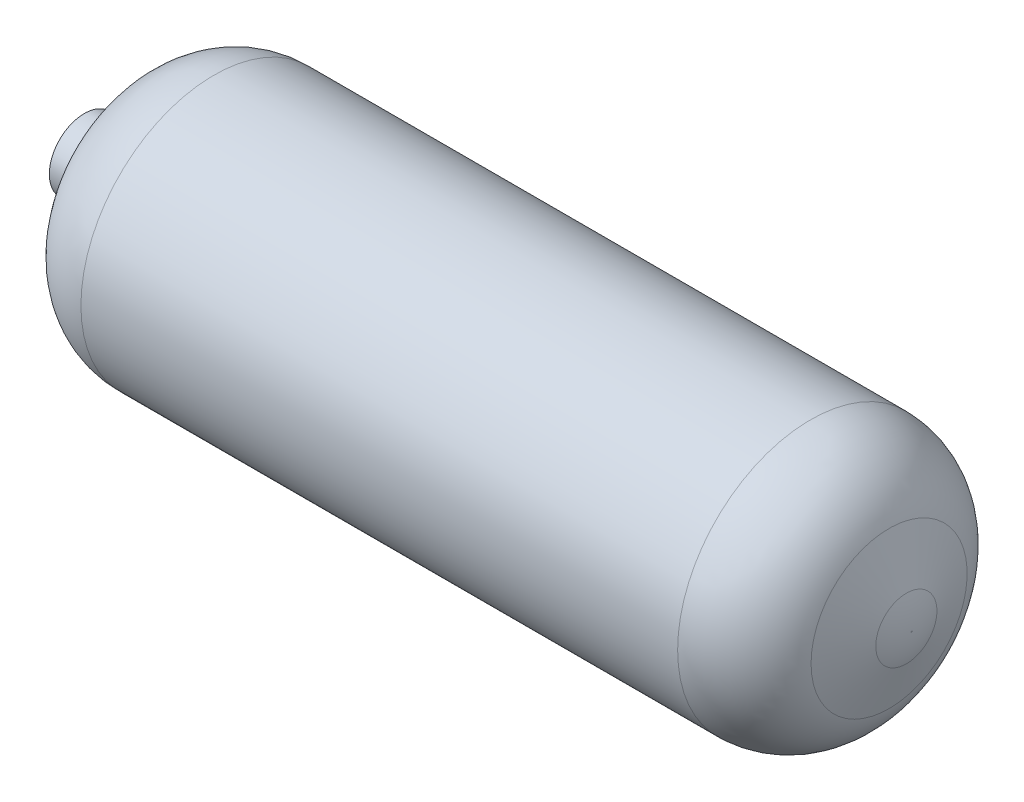
SolidWorks part; units mm, degrees
material "6061-T6 (SS)"
ref_plane "Front Plane" through (0, 0, 0) normal (0, 0, 1) x (1, 0, 0)
ref_plane "Top Plane" through (0, 0, 0) normal (0, 1, 0) x (1, 0, 0)
ref_plane "Right Plane" through (0, 0, 0) normal (1, 0, 0) x (0, 0, -1)
sketch "Sketch1" plane through (0, 0, 0) normal (0, 0, 1) x (1, 0, 0)
  line L0 (-0.2756, 0.129) -> (0.3032, 0.129)
  line L1 (-0.4012, 0.034) -> (-0.4012, 0)
  line L2 (-0.4012, 0.034) -> (-0.3773, 0.034)
  line L4 (-0.3729, 0.0367) -> (-0.3487, 0.0842)
  line L5 (-0.4012, 0) -> (0.4012, 0) construction
  line L6 (0.3794, 0.0757) -> (0.3961, 0.0297)
  line L7 (-0.4012, 0) -> (0.4012, 0)
  line L8 (0.4012, 0) -> (0.4012, 0.0006)
  arc A0 (-0.2756, 0.129) -> (-0.3487, 0.0842) centre (-0.2756, 0.047) ccw
  arc A1 (0.3032, 0.129) -> (0.3794, 0.0757) centre (0.3032, 0.048) cw
  arc A2 (0.4012, 0.0006) -> (0.3961, 0.0297) centre (0.3163, 0.0006) ccw
  arc A3 (-0.3729, 0.0367) -> (-0.3773, 0.034) centre (-0.3773, 0.039) cw
  point P6 (-0.3742, 0.034)
  dimension "D8" = 0.082
  dimension "D11" = 0.081
  dimension "D13" = 0.085
  dimension "D6" = 0.005
  dimension "D2" = 0.2756
  dimension "D3" = 0.034
  dimension "D4" = 0.3032
  dimension "D5" = 0.027
  dimension "D7" = 117
  dimension "D9" = 0.8025
  dimension "D10" = 110
revolve "Revolve2" add sketch "Sketch1" angle 360 about L7 region at (0.0088, 0.062, 0)
scale "Scale1" scale about origin uniform scaling yes scale factor 649.767462
shell "Shell2" [suppressed] thickness 5.588
sketch "Sketch2" plane through (0, 0, 0) normal (0, 1, 0) x (1, 0, 0)
  line L7 (246.4991, 49.1898) -> (257.3884, 19.2716)
  line L8 (260.7192, 0.3818) -> (197.042, 0.3818)
  line L9 (197.042, -83.82) -> (197.042, 83.82) construction
  line L10 (197.042, 0.3818) -> (197.042, 83.82)
  line L11 (-226.5465, 54.7281) -> (-242.2713, 23.8664)
  line L12 (-260.7192, 22.0921) -> (-245.1667, 22.0921)
  line L13 (-260.7192, 22.0921) -> (-260.7192, 0)
  line L14 (-260.7192, 22.0921) -> (-260.7192, -22.0921) construction
  line L15 (-260.7192, 0) -> (-179.0728, 0)
  line L16 (-179.0728, -83.82) -> (-179.0728, 83.82) construction
  line L17 (-179.0728, 0) -> (-179.0728, 83.82)
  arc A2 (197.042, 83.82) -> (246.4991, 49.1898) centre (197.042, 31.1888) cw
  arc A3 (257.3884, 19.2716) -> (260.7192, 0.3818) centre (205.489, 0.3818) cw
  arc A4 (-179.0728, 83.82) -> (-226.5465, 54.7281) centre (-179.0728, 30.5391) ccw
  arc A5 (-242.2713, 23.8664) -> (-245.1667, 22.0921) centre (-245.1667, 25.3417) cw
revolve "Added to make cavity cut for shoulder" [suppressed] add sketch "Sketch2" angle 360 about L15
